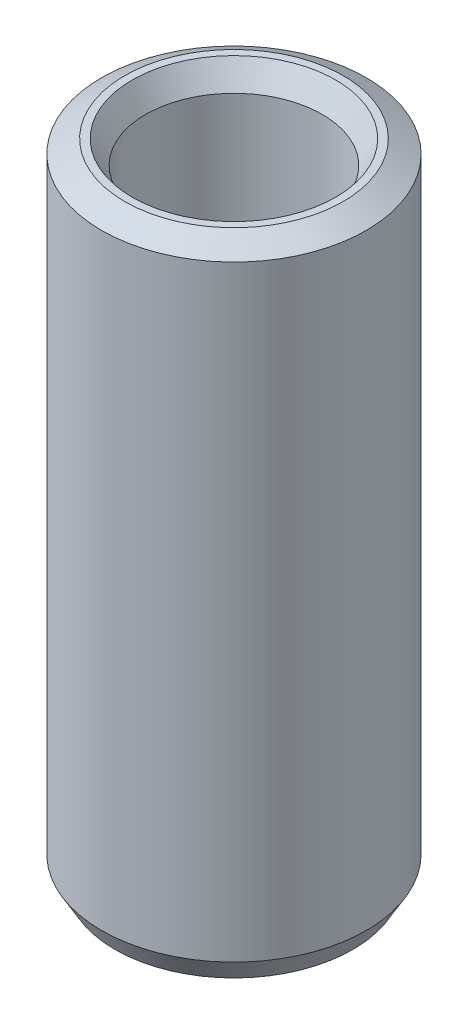
SolidWorks part; units mm, degrees
ref_plane "Front Plane" through (0, 0, 0) normal (0, 0, 1) x (1, 0, 0)
ref_plane "Top Plane" through (0, 0, 0) normal (0, 1, 0) x (1, 0, 0)
ref_plane "Right Plane" through (0, 0, 0) normal (1, 0, 0) x (0, 0, -1)
sketch "Sketch1" plane through (0, 0, 0) normal (0, 1, 0) x (1, 0, 0)
  circle A0 centre (0, 0) radius 22.5
  dimension "SLEEVE_OD" = 45
extrude "Boss-Extrude1" add sketch "Sketch1" along normal blind 109.2981
sketch "Sketch2" plane through (0, 0, 0) normal (0, 1, 0) x (1, 0, 0)
  circle A0 centre (0, 0) radius 15.0124
  dimension "BORE_D" = 30.0249
extrude "Cut-Extrude1" cut sketch "Sketch2" along normal through all
chamfer "Chamfer1" distance 2.2745 angle 60 4 edges at (0, 109.2981, 15.0124) (0, 0, 15.0124) (0, 0, 22.5) (0, 109.2981, 22.5) first distance on face at (0, 109.2981, 15.0124) first distance on face at (0, 0, 15.0124) first distance on face at (0, 109.2981, 22.5)
